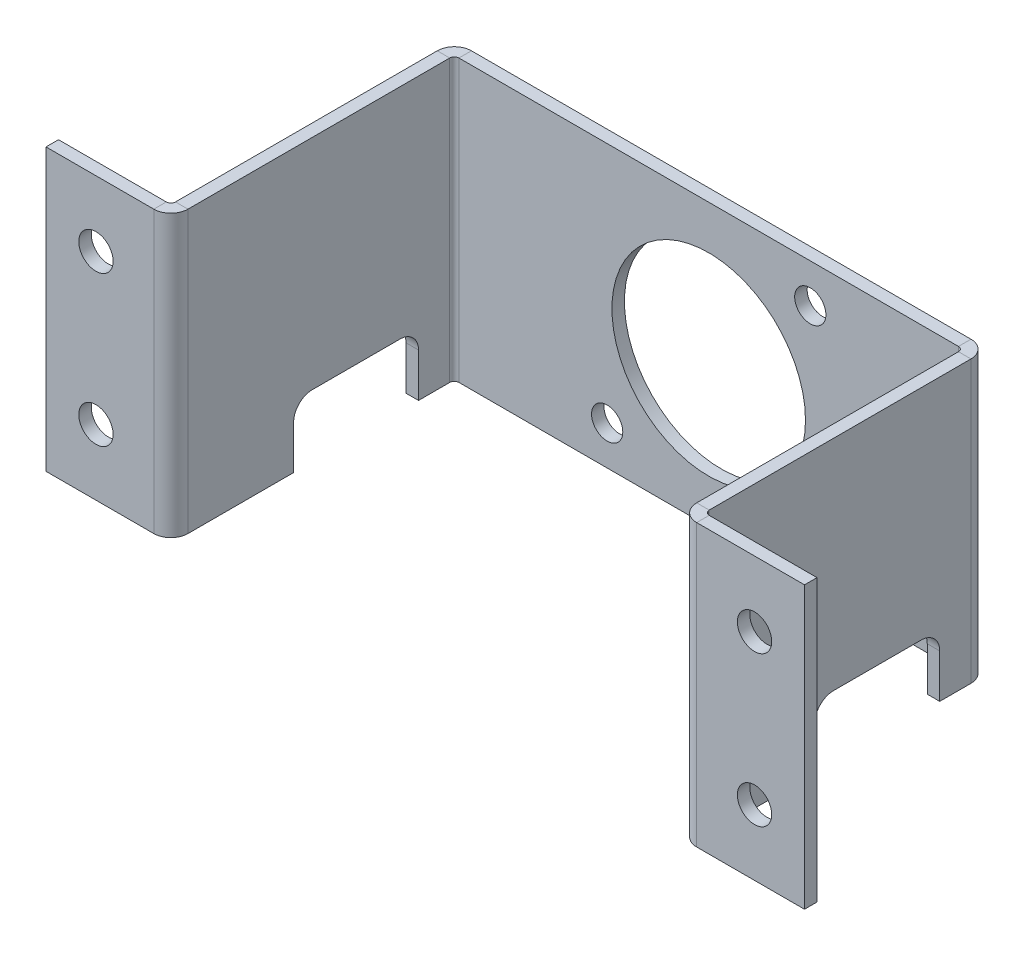
SolidWorks part; units mm, degrees
note: The reader was unsure of these and kept them because the rebuilt part matched: flange length of "Edge-Flange1", "Edge-Flange2", "Edge-Flange3".
material "1.0037 (S235JR)"
ref_plane "Front Plane" through (0, 0, 0) normal (0, 0, 1) x (1, 0, 0)
ref_plane "Top Plane" through (0, 0, 0) normal (0, 1, 0) x (1, 0, 0)
ref_plane "Right Plane" through (0, 0, 0) normal (1, 0, 0) x (0, 0, -1)
sketch "Sketch2" plane through (0, 0, 0) normal (0, 0, 1) x (1, 0, 0)
  line L1 (-40, 22.5) -> (40, 22.5)
  line L2 (-40, 22.5) -> (-40, -22.5)
  line L3 (-40, -22.5) -> (40, -22.5)
  line L4 (40, 22.5) -> (40, -22.5)
  line L5 (-40, 22.5) -> (40, -22.5) construction
  line L6 (-40, -22.5) -> (40, 22.5) construction
  point P0 (0, 0)
  dimension "D1" = 45
  dimension "D2" = 80
base flange "Base-Flange1" sketch "Sketch2" thickness 2 reverse thickness direction no parameters "D1"=0.7366
edge flange "Edge-Flange1" sketch "Sketch9" flange angle 90 flange length 44.66 flange position bend outside bend radius 0.7366 thickness 2 relief rectangular parameters "D6"=10
sketch "Sketch9" plane through (40, 0, 0) normal (-1, 0, 0) x (0, -1, 0)
  line L2 (-22.5, 0) -> (-22.5, 42.66)
  line L3 (-22.5, 42.66) -> (22.5, 42.66)
  line L4 (22.5, 42.66) -> (22.5, 0)
  line L5 (22.5, 0) -> (-22.5, 0) construction
  line L6 (22.5, 0) -> (-22.5, 0)
bend "EdgeBend1" bend radius 0.7366 bend angle 90 parameters "D5"=1
edge flange "Edge-Flange2" sketch "Sketch12" flange angle 90 flange length 44.66 flange position bend outside bend radius 0.7366 thickness 2 relief rectangular parameters "D6"=10
sketch "Sketch12" plane through (-40, 0, 0) normal (1, 0, 0) x (0, 1, 0)
  line L2 (-22.5, 0) -> (-22.5, 42.66)
  line L3 (-22.5, 42.66) -> (22.5, 42.66)
  line L4 (22.5, 42.66) -> (22.5, 0)
  line L5 (22.5, 0) -> (-22.5, 0) construction
  line L6 (22.5, 0) -> (-22.5, 0)
bend "EdgeBend2" bend radius 0.7366 bend angle 90 parameters "D5"=2
sketch "Sketch13" plane through (0, 0, 0) normal (0, 0, 1) x (1, 0, 0)
  circle A0 centre (0, 0) radius 15.5
  dimension "D1" = 31
extrude "Cut-Extrude1" cut sketch "Sketch13" against normal through all normal cut yes
sketch "Sketch14" plane through (0, 0, 0) normal (0, 0, 1) x (1, 0, 0)
  line L0 (0, 0) -> (-25.7234, -25.7234) construction
  line L1 (-25.7234, -25.7234) -> (33.035, 33.035) construction
  circle A0 centre (-16.2635, -16.2635) radius 2.5
  circle A1 centre (16.2635, 16.2635) radius 2.5
  dimension "D3" = 5
  dimension "D1" = 23
  dimension "D2" = 23
extrude "Cut-Extrude2" cut sketch "Sketch14" against normal through all normal cut yes
edge flange "Edge-Flange3" sketch "Sketch19" flange profiles "Sketch19", "Sketch20" flange angle 90 flange length 20 flange position bend outside bend radius 0.7366 thickness 2 relief rectangular parameters "D6"=10, "D8"=1
sketch "Sketch19" plane through (42.7366, 0, 42.66) normal (0, 0, -1) x (0, 1, 0)
  line L2 (-22.5, 0) -> (-22.5, 18)
  line L3 (-22.5, 18) -> (22.5, 18)
  line L4 (22.5, 18) -> (22.5, 0)
  line L5 (22.5, 0) -> (-22.5, 0) construction
  line L6 (22.5, 0) -> (-22.5, 0)
sketch "Sketch20" plane through (-42.7366, 0, 42.66) normal (0, 0, -1) x (0, -1, 0)
  line L0 (22.5, 0) -> (-22.5, 0) construction
  line L1 (22.5, 0) -> (-22.5, 0)
  line L2 (22.5, 0) -> (22.5, 18)
  line L3 (22.5, 18) -> (-22.5, 18)
  line L4 (-22.5, 18) -> (-22.5, 0)
bend "EdgeBend3" bend radius 0.7366 bend angle 90 parameters "D5"=3
bend "EdgeBend4" bend radius 0.7366 bend angle 90 parameters "D5"=4
sketch "Sketch21" plane through (0, 0, 45.3966) normal (0, 0, 1) x (1, 0, 0)
  line L0 (-60.7366, -22.5) -> (-60.7366, 22.5) construction
  line L1 (60.7366, 22.5) -> (60.7366, -22.5) construction
  circle A0 centre (52.7366, 12) radius 2.75
  circle A1 centre (52.7366, -12) radius 2.75
  circle A2 centre (-52.7366, 12) radius 2.75
  circle A3 centre (-52.7366, -12) radius 2.75
  dimension "D1" = 5.5
  dimension "D2" = 8
  dimension "D3" = 8
  dimension "D4" = 12
  dimension "D5" = 12
  dimension "D6" = 8
  dimension "D7" = 8
  dimension "D8" = 12
  dimension "D9" = 12
extrude "Cut-Extrude3" cut sketch "Sketch21" against normal through all normal cut yes
sketch "Sketch22" plane through (42.7366, 0, 0) normal (1, 0, 0) x (0, 0, -1)
  line L0 (-0.7366, -22.5) -> (-42.66, -22.5) construction
  line L1 (-5.7366, -22.5) -> (-25.7366, -22.5)
  line L2 (-5.7366, -22.5) -> (-5.7366, -15.5)
  line L3 (-8.7366, -12.5) -> (-22.7366, -12.5)
  line L4 (-25.7366, -22.5) -> (-25.7366, -15.5)
  line L5 (-0.7366, -22.5) -> (-0.7366, 22.5) construction
  arc A0 (-5.7366, -15.5) -> (-8.7366, -12.5) centre (-8.7366, -15.5) ccw
  arc A1 (-22.7366, -12.5) -> (-25.7366, -15.5) centre (-22.7366, -15.5) ccw
  point P10 (-5.7366, -12.5)
  point P13 (-25.7366, -12.5)
  dimension "D4" = 3
  dimension "D1" = 20
  dimension "D2" = 10
  dimension "D3" = 5
extrude "Cut-Extrude4" cut sketch "Sketch22" against normal through all normal cut yes
sketch "Bend-Lines1" [suppressed] plane through (0, 0, 0) normal (0, 1, 0) x (1, 0, 0)
sketch "Bounding-Box1" [suppressed] plane through (0, 0, 0) normal (0, 1, 0) x (1, 0, 0)
sheet metal parameters "Sheet-Metal1" thickness 2 parameters "D1"=0.7366
flat pattern "Flat-Pattern1" [suppressed]
sketch "Bend-Lines2" plane through (0, 0, 0) normal (0, 1, 0) x (1, 0, 0)
sketch "Bounding-Box2" [suppressed] plane through (0, 0, 0) normal (0, 1, 0) x (1, 0, 0)
sheet metal parameters "Sheet-Metal2" thickness 2 parameters "D1"=0.7366
flat pattern "Flat-Pattern1" [suppressed]
sketch "Bend-Lines2" plane through (0, 0, 0) normal (0, 1, 0) x (1, 0, 0)
sketch "Bounding-Box2" [suppressed] plane through (0, 0, 0) normal (0, 1, 0) x (1, 0, 0)
bend of the flat pattern "Flatten-<EdgeBend1>1"
sheet metal parameters "Sheet-Metal3" thickness 2 parameters "D1"=0.7366
flat pattern "Flat-Pattern1" [suppressed]
sketch "Bend-Lines2" plane through (0, 0, 0) normal (0, 1, 0) x (1, 0, 0)
sketch "Bounding-Box2" [suppressed] plane through (0, 0, 0) normal (0, 1, 0) x (1, 0, 0)
bend of the flat pattern "Flatten-<EdgeBend1>1"
bend of the flat pattern "Flatten-<EdgeBend2>1"
sheet metal parameters "Sheet-Metal4" thickness 2 parameters "D1"=0.7366
flat pattern "Flat-Pattern1" [suppressed]
sketch "Bend-Lines2" plane through (0, 0, 0) normal (0, 1, 0) x (1, 0, 0)
sketch "Bounding-Box2" [suppressed] plane through (0, 0, 0) normal (0, 1, 0) x (1, 0, 0)
bend of the flat pattern "Flatten-<EdgeBend1>1"
bend of the flat pattern "Flatten-<EdgeBend2>1"
sheet metal parameters "Sheet-Metal5" thickness 2 parameters "D1"=0.7366
flat pattern "Flat-Pattern1" [suppressed]
sketch "Bend-Lines2" plane through (0, 0, 0) normal (0, 1, 0) x (1, 0, 0)
sketch "Bounding-Box2" [suppressed] plane through (0, 0, 0) normal (0, 1, 0) x (1, 0, 0)
bend of the flat pattern "Flatten-<EdgeBend1>1"
bend of the flat pattern "Flatten-<EdgeBend2>1"
sheet metal parameters "Sheet-Metal6" thickness 2 parameters "D1"=0.7366
flat pattern "Flat-Pattern1" [suppressed]
sketch "Bend-Lines2" plane through (0, 0, 0) normal (0, 1, 0) x (1, 0, 0)
sketch "Bounding-Box2" [suppressed] plane through (0, 0, 0) normal (0, 1, 0) x (1, 0, 0)
bend of the flat pattern "Flatten-<EdgeBend1>1"
bend of the flat pattern "Flatten-<EdgeBend2>1"
bend of the flat pattern "Flatten-<EdgeBend3>1"
bend of the flat pattern "Flatten-<EdgeBend4>1"
sheet metal parameters "Sheet-Metal7" thickness 2 parameters "D1"=0.7366
flat pattern "Flat-Pattern1" [suppressed]
sketch "Bend-Lines2" plane through (0, 0, 0) normal (0, 1, 0) x (1, 0, 0)
sketch "Bounding-Box2" [suppressed] plane through (0, 0, 0) normal (0, 1, 0) x (1, 0, 0)
bend of the flat pattern "Flatten-<EdgeBend1>1"
bend of the flat pattern "Flatten-<EdgeBend2>1"
bend of the flat pattern "Flatten-<EdgeBend3>1"
bend of the flat pattern "Flatten-<EdgeBend4>1"
sheet metal parameters "Sheet-Metal8" thickness 2 parameters "D1"=0.7366
flat pattern "Flat-Pattern1"
sketch "Bend-Lines2" plane through (0, 0, 0) normal (0, 0, 1) x (1, 0, 0)
  line L0 (-86.0152, 22.5) -> (-86.0152, -22.5) construction
  line L1 (86.0152, -22.5) -> (86.0152, 22.5) construction
  line L2 (-41.3639, 22.5) -> (-41.3639, -22.5) construction
  line L3 (41.3639, -22.5) -> (41.3639, 22.5) construction
  line L4 (-86.0152, 22.5) -> (-86.0152, -22.5) construction
  line L5 (86.0152, -22.5) -> (86.0152, 22.5) construction
  line L6 (-41.3639, 22.5) -> (-41.3639, -22.5) construction
  line L7 (41.3639, -22.5) -> (41.3639, 22.5) construction
sketch3d "Bounding-Box2" [suppressed]
  line L0 (-104.6425, -22.5, 0) -> (104.6425, -22.5, 0) construction
  line L1 (-104.6425, 22.5, 0) -> (104.6425, 22.5, 0) construction
  line L2 (-104.6425, -22.5, 0) -> (-104.6425, 22.5, 0) construction
  line L3 (104.6425, -22.5, 0) -> (104.6425, 22.5, 0) construction
bend of the flat pattern "Flatten-<EdgeBend1>1"
bend of the flat pattern "Flatten-<EdgeBend2>1"
bend of the flat pattern "Flatten-<EdgeBend3>1"
bend of the flat pattern "Flatten-<EdgeBend4>1"
